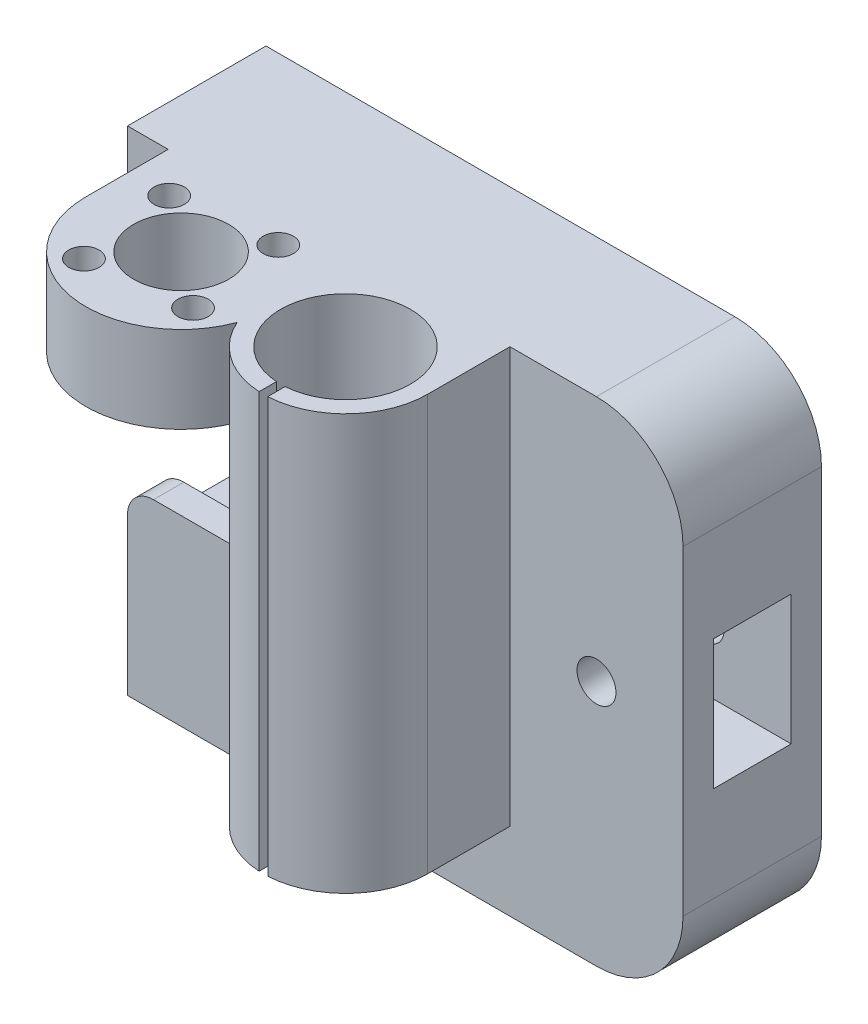
SolidWorks part; units mm, degrees
ref_plane "Front Plane" through (0, 0, 0) normal (0, 0, 1) x (1, 0, 0)
ref_plane "Top Plane" through (0, 0, 0) normal (0, 1, 0) x (1, 0, 0)
ref_plane "Right Plane" through (0, 0, 0) normal (1, 0, 0) x (0, 0, -1)
sketch "Sketch1" plane through (0, 0, 0) normal (0, 1, 0) x (1, 0, 0)
  line L0 (0, 0) -> (64.191, 0)
  line L1 (64.191, 0) -> (64.191, -16)
  line L2 (34.191, -32.9833) -> (34.191, -34.9868)
  line L3 (0, 0) -> (0, -16)
  line L4 (15.691, -25.5) -> (34.691, -25.5) construction
  line L5 (15.691, -25.5) -> (15.691, 0) construction
  line L6 (15.691, -25.5) -> (15.691, -33.5) construction
  line L7 (10.7657, -31.8041) -> (20.6163, -19.1959) construction
  line L8 (9.3869, -20.5747) -> (21.9951, -30.4253) construction
  line L9 (35.191, -32.9833) -> (35.191, -34.9868)
  line L10 (34.691, -25.5) -> (34.691, -32.9833) construction
  line L11 (34.191, -32.9833) -> (35.191, -32.9833) construction
  line L12 (34.191, -34.9868) -> (35.191, -34.9868) construction
  line L13 (64.191, -16) -> (44.191, -16)
  line L14 (44.191, -16) -> (44.191, -25.5)
  line L15 (0, -16) -> (4.691, -16)
  line L16 (4.691, -16) -> (4.691, -25.5)
  circle A0 centre (15.691, -25.5) radius 5.5
  arc A1 (35.191, -32.9833) -> (34.191, -32.9833) centre (34.691, -25.5) ccw
  arc A2 (35.191, -34.9868) -> (44.191, -25.5) centre (34.691, -25.5) ccw
  circle A3 centre (15.691, -25.5) radius 8 construction
  circle A4 centre (10.7657, -31.8041) radius 1.75
  circle A5 centre (9.3869, -20.5747) radius 1.75
  circle A6 centre (20.6163, -19.1959) radius 1.75
  circle A7 centre (21.9951, -30.4253) radius 1.75
  arc A8 (4.691, -25.5) -> (26.0002, -29.3367) centre (15.691, -25.5) ccw
  arc A9 (26.0002, -29.3367) -> (34.191, -34.9868) centre (34.691, -25.5) ccw
  dimension "D1" = 19
  dimension "D2" = 15
  dimension "D3" = 11
  dimension "D5" = 2
  dimension "D6" = 16
  dimension "D7" = 38
  dimension "D8" = 3.5
  dimension "D9" = 22
  dimension "D10" = 1
  dimension "D4" = 25.5
  dimension "D11" = 16
  dimension "D12" = 20
  dimension "D13" = 4.691
extrude "Boss-Extrude1" add sketch "Sketch1" along normal mid plane 57 contours A8 A2 L0 | A2 A8 A0 A4 A5 A6 A7 | A8 A2 L2 A1 L9 | A2 A8 region at (29.3649, 0, 12.581)
sketch "Sketch2" plane through (0, 0, 16) normal (0, 0, 1) x (1, 0, 0)
  line L0 (4.691, 28.5) -> (4.691, -28.5) construction
  line L1 (4.691, 18.5) -> (26.0002, 18.5)
  line L2 (4.691, 18.5) -> (4.691, -28.5)
  line L3 (4.691, -28.5) -> (44.191, -28.5)
  line L5 (26.0002, 28.5) -> (4.691, 28.5) construction
  line L6 (26.0002, 18.5) -> (26.0002, -19.5)
  line L7 (26.0002, -19.5) -> (44.191, -19.5)
  line L8 (44.191, 28.5) -> (44.191, -28.5) construction
  line L9 (44.191, -19.5) -> (44.191, -28.5)
  dimension "D1" = 10
  dimension "D2" = 9
  dimension "D3" = 21.3092
extrude "Cut-Extrude1" cut sketch "Sketch2" along normal through all
sketch "Sketch3" plane through (0, 0, 0) normal (-1, 0, 0) x (0, 0, 1)
  line L0 (8, 28.5) -> (8, 12.5) construction
  line L1 (3.5, 12.5) -> (12.5, 12.5)
  line L2 (3.5, 12.5) -> (3.5, -12.5)
  line L3 (3.5, -12.5) -> (12.5, -12.5)
  line L4 (12.5, 12.5) -> (12.5, -12.5)
  line L5 (0, 28.5) -> (16, 28.5) construction
  line L6 (0, 0) -> (3.5, 0) construction
  line L7 (0, 28.5) -> (0, -28.5) construction
  line L8 (0, -28.5) -> (16, -28.5) construction
  dimension "D1" = 3.5
  dimension "D2" = 16
  dimension "D3" = 25
extrude "Cut-Extrude2" cut sketch "Sketch3" against normal blind 28
sketch "Sketch4" plane through (0, 0, 0) normal (-1, 0, 0) x (0, 0, 1)
  line L0 (16, 28.5) -> (16, -28.5) construction
  line L1 (0, 7.4) -> (16, 7.4)
  line L2 (0, 7.4) -> (0, -7.4)
  line L3 (0, -7.4) -> (16, -7.4)
  line L4 (16, 7.4) -> (16, -7.4)
  point P4 (0, 0)
  point P9 (8, 7.4)
  dimension "D1" = 14.8
extrude "Cut-Extrude3" cut sketch "Sketch4" against normal up to surface (26.0002 mm away) up to face at (26.0002, -0.5, 22.6683)
hole_wizard "M4 Clearance Hole1" positions "3DSketch1" profile "Sketch5" hole size "M4" standard "ANSI Metric" end condition through all
sketch3d "3DSketch1"
  line L0 (54.191, 0, 16) -> (64.191, 0, 16) construction
  line L6 (64.191, 28.5, 16) -> (64.191, -28.5, 16) construction
  point P0 (54.191, 0, 16)
  dimension "D1" = 10
sketch "Sketch5" plane through (54.191, 0, 16) normal (1, 0, 0) x (0, -1, 0)
  line L0 (0, 0) -> (0, 16)
  line L1 (0, 16) -> (2.25, 16)
  line L2 (2.25, 16) -> (2.25, 0)
  line L5 (2.25, 0) -> (0, 0)
  line L11 (0, -6.35) -> (0, 107.95) construction
  dimension "Thru Hole Dia." = 4.5
  dimension "Thru Hole Depth" = 16
sketch "Sketch6" plane through (0, 0, 0) normal (-1, 0, 0) x (0, 0, 1)
  line L0 (8, -22.5) -> (8, 22.5) construction
  line L1 (8, 22.5) -> (8, 28.5) construction
  line L2 (8, -22.5) -> (8, -28.5) construction
  line L3 (0, -28.5) -> (16, -28.5) construction
  line L4 (0, 28.5) -> (16, 28.5) construction
  circle A0 centre (8, 22.5) radius 4.1
  circle A1 centre (8, -22.5) radius 3.9945
  dimension "D1" = 45
  dimension "D2" = 8.2
extrude "Cut-Extrude4" cut sketch "Sketch6" against normal blind 30 contours A1 | A0 | A0 region at (0, 22.5, 8) region at (0, -22.5, 8)
sketch "Sketch7" plane through (28, 0, 0) normal (-1, 0, 0) x (0, 0, 1)
  line L0 (0, 0) -> (3.5, 0) construction
  line L1 (3.5, 7.5) -> (12.5, 7.5)
  line L2 (3.5, 7.5) -> (3.5, -7.5)
  line L3 (3.5, -7.5) -> (12.5, -7.5)
  line L4 (12.5, 7.5) -> (12.5, -7.5)
  line L5 (8, 7.5) -> (8, 12.5) construction
  line L6 (12.5, 12.5) -> (3.5, 12.5) construction
  line L7 (12.5, -12.5) -> (12.5, 12.5) construction
  dimension "D1" = 15
extrude "Cut-Extrude5" cut sketch "Sketch7" against normal through all
fillet "Fillet1" radius 10 2 edges at (64.191, 28.5, 8) (64.191, -28.5, 8)
fillet "Fillet2" radius 3 4 edges at (0, -7.4, 14.25) (0, -7.4, 1.75) (0, 7.4, 14.25) (0, 7.4, 1.75)
